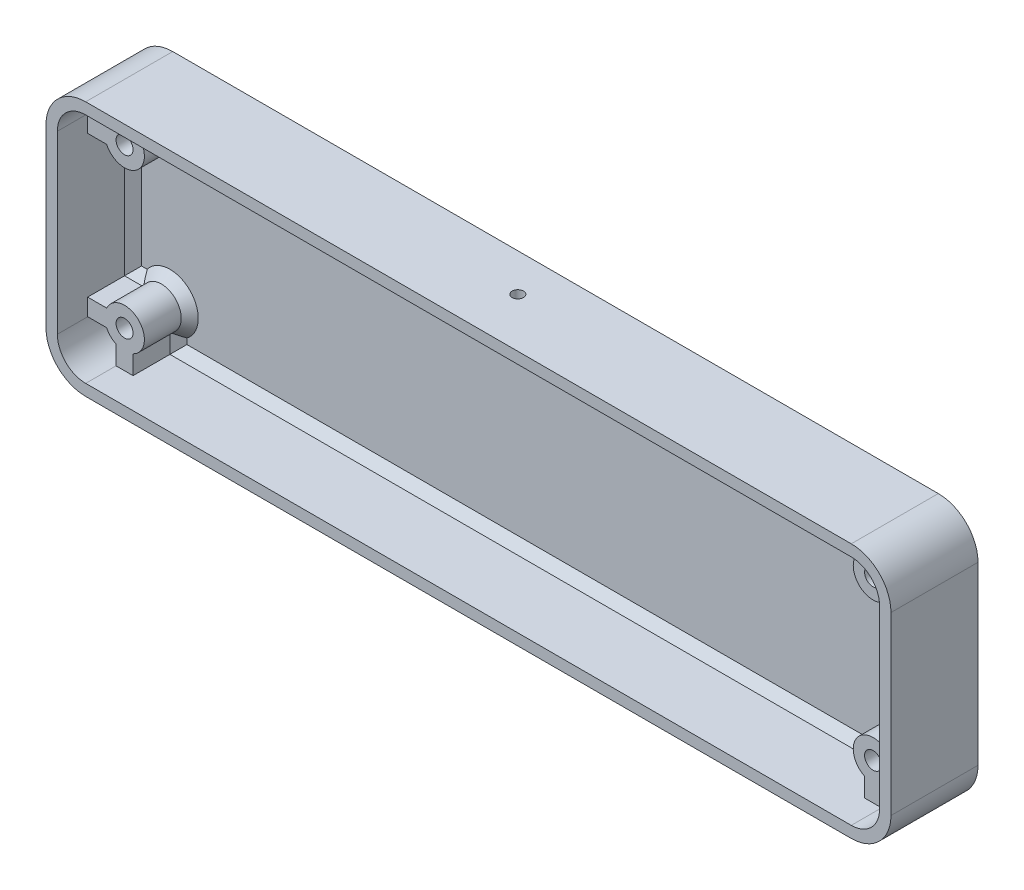
SolidWorks part; units mm, degrees
ref_plane "Alzado" through (0, 0, 0) normal (0, 0, 1) x (1, 0, 0)
ref_plane "Planta" through (0, 0, 0) normal (0, 1, 0) x (1, 0, 0)
ref_plane "Vista lateral" through (0, 0, 0) normal (1, 0, 0) x (0, 0, -1)
sketch "Croquis1" plane through (0, 0, 0) normal (0, 0, 1) x (1, 0, 0)
  line L0 (-67.5, 22.5) -> (67.5, 22.5)
  line L1 (-70, -18) -> (70, -18) construction
  line L2 (-70, -18) -> (-70, 18) construction
  line L3 (-70, 18) -> (70, 18) construction
  line L4 (70, -18) -> (70, 18) construction
  line L5 (-70, -18) -> (70, 18) construction
  line L6 (-70, 18) -> (70, -18) construction
  line L7 (-67.5, 20.5) -> (67.5, 20.5)
  line L8 (-72.5, 15.5) -> (-72.5, -15.5)
  line L9 (-67.5, -20.5) -> (67.5, -20.5)
  line L10 (72.5, 15.5) -> (72.5, -15.5)
  line L11 (-72.5, 20.5) -> (72.5, -20.5) construction
  line L12 (-72.5, -20.5) -> (72.5, 20.5) construction
  line L13 (74.5, 15.5) -> (74.5, -15.5)
  line L14 (-67.5, -22.5) -> (67.5, -22.5)
  line L15 (-74.5, 15.5) -> (-74.5, -15.5)
  arc A0 (67.5, 20.5) -> (72.5, 15.5) centre (67.5, 15.5) cw
  arc A1 (67.5, -20.5) -> (72.5, -15.5) centre (67.5, -15.5) ccw
  arc A2 (-67.5, -20.5) -> (-72.5, -15.5) centre (-67.5, -15.5) cw
  arc A3 (-72.5, 15.5) -> (-67.5, 20.5) centre (-67.5, 15.5) cw
  arc A4 (67.5, 22.5) -> (74.5, 15.5) centre (67.5, 15.5) cw
  arc A5 (67.5, -22.5) -> (74.5, -15.5) centre (67.5, -15.5) ccw
  arc A6 (-67.5, -22.5) -> (-74.5, -15.5) centre (-67.5, -15.5) cw
  arc A7 (-74.5, 15.5) -> (-67.5, 22.5) centre (-67.5, 15.5) cw
  circle A8 centre (66, 14) radius 1.5
  circle A9 centre (66, -14) radius 1.5
  circle A10 centre (-66, 14) radius 1.5
  circle A11 centre (-66, -14) radius 1.5
  circle A12 centre (-66, 14) radius 3.5
  circle A13 centre (66, 14) radius 3.5
  circle A14 centre (66, -14) radius 3.5
  circle A15 centre (-66, -14) radius 3.5
  point P0 (0, 0)
  point P6 (0, 0)
  dimension "D5" = 5
  dimension "D7" = 3
  dimension "D8" = 4
  dimension "D9" = 4
  dimension "D11" = 4
  dimension "D12" = 2
  dimension "D1" = 140
  dimension "D2" = 36
  dimension "D3" = 145
  dimension "D4" = 41
  dimension "D10" = 4
  dimension "D6" = 2
  dimension "D13" = 2
  dimension "D14" = 2
  dimension "D15" = 2
extrude "Saliente-Extruir1" add sketch "Croquis1" against normal blind 15.35 contours A7 L15 A6 L14 A5 L13 A4 L0 L8 A3 L7 A0 L10 A1 L9 A2 | A13 A8 | A14 A9 | A12 A10 | A15 A11 region at (0, 20.9435, 0) region at (-69.401, 14, 0) region at (62.599, 14, 0) region at (62.599, -14, 0) region at (-69.401, -14, 0)
sketch "Croquis3" plane through (0, 0, -15.35) normal (0, 0, -1) x (-1, 0, 0)
  line L0 (72.5, 15.5) -> (72.5, -15.5) construction
  line L1 (67.5, -20.5) -> (-67.5, -20.5) construction
  line L2 (-72.5, 15.5) -> (-72.5, -15.5) construction
  line L3 (67.5, 20.5) -> (-67.5, 20.5) construction
  line L4 (72.5, 15.5) -> (72.5, -15.5)
  line L5 (67.5, -20.5) -> (-67.5, -20.5)
  line L6 (-72.5, 15.5) -> (-72.5, -15.5)
  line L7 (67.5, 20.5) -> (-67.5, 20.5)
  arc A0 (67.5, -20.5) -> (72.5, -15.5) centre (67.5, -15.5) ccw construction
  arc A1 (72.5, 15.5) -> (67.5, 20.5) centre (67.5, 15.5) ccw construction
  arc A2 (-72.5, -15.5) -> (-67.5, -20.5) centre (-67.5, -15.5) ccw construction
  arc A3 (-67.5, 20.5) -> (-72.5, 15.5) centre (-67.5, 15.5) ccw construction
  arc A4 (67.5, -20.5) -> (72.5, -15.5) centre (67.5, -15.5) ccw
  arc A5 (72.5, 15.5) -> (67.5, 20.5) centre (67.5, 15.5) ccw
  arc A6 (-72.5, -15.5) -> (-67.5, -20.5) centre (-67.5, -15.5) ccw
  arc A7 (-67.5, 20.5) -> (-72.5, 15.5) centre (-67.5, 15.5) ccw
extrude "Saliente-Extruir2" add sketch "Croquis3" against normal blind 2
sketch "Croquis5" plane through (0, 0, 0) normal (0, 0, 1) x (1, 0, 0)
  circle A0 centre (66, -14) radius 1.5 construction
  circle A1 centre (66, -14) radius 3.5 construction
  circle A2 centre (66, 14) radius 1.5 construction
  circle A3 centre (66, 14) radius 3.5 construction
  circle A4 centre (-66, -14) radius 1.5 construction
  circle A5 centre (-66, -14) radius 3.5 construction
  circle A6 centre (-66, 14) radius 1.5 construction
  circle A7 centre (-66, 14) radius 3.5 construction
  circle A8 centre (66, -14) radius 1.5
  circle A9 centre (66, -14) radius 3.5
  circle A10 centre (66, 14) radius 1.5
  circle A11 centre (66, 14) radius 3.5
  circle A12 centre (-66, -14) radius 1.5
  circle A13 centre (-66, -14) radius 3.5
  circle A14 centre (-66, 14) radius 1.5
  circle A15 centre (-66, 14) radius 3.5
extrude "Cortar-Extruir1" cut sketch "Croquis5" against normal blind 5.35
sketch "Croquis6" plane through (0, 0, -5.35) normal (0, 0, 1) x (1, 0, 0)
  line L0 (-69.1623, -12.5) -> (-72.5, -12.5)
  line L1 (-72.5, 15.5) -> (-72.5, -15.5) construction
  line L2 (-69.1623, -15.5) -> (-72.5, -15.5)
  line L3 (-72.5, -12.5) -> (-72.5, -15.5)
  line L4 (-68.336, -12.5) -> (-72.5, -12.5) construction
  line L5 (-68.336, -15.5) -> (-72.5, -15.5) construction
  line L6 (-64.5, -17.1623) -> (-64.5, -20.5)
  line L7 (67.5, -20.5) -> (-67.5, -20.5) construction
  line L8 (-67.5, -17.1623) -> (-67.5, -20.5)
  line L9 (-67.5, -16.2401) -> (-67.5, -20.5) construction
  line L10 (-64.5, -16.2401) -> (-64.5, -20.5) construction
  line L11 (-64.5, -20.5) -> (-67.5, -20.5)
  line L12 (-72.5, 12.5) -> (-69.1623, 12.5)
  line L13 (-72.5, -15.5) -> (-72.5, 15.5) construction
  line L14 (-72.5, 15.5) -> (-69.1623, 15.5)
  line L15 (-72.5, 15.5) -> (-72.5, 12.5)
  line L16 (-64.5, 17.1623) -> (-64.5, 20.5)
  line L17 (-67.5, 20.5) -> (67.5, 20.5) construction
  line L18 (-67.5, 17.1623) -> (-67.5, 20.5)
  line L19 (-72.5, 15.5) -> (-66.5585, 15.5) construction
  line L20 (-67.5, 14) -> (-67.5, 20.5) construction
  line L21 (-72.5, 12.5) -> (-66.5585, 12.5) construction
  line L22 (-64.5, 14) -> (-64.5, 20.5) construction
  line L23 (-67.5, 20.5) -> (-64.5, 20.5)
  line L24 (0, 8.9423) -> (0, -8.2588) construction
  line L25 (72.5, -12.5) -> (72.5, -15.5)
  line L26 (69.1623, -12.5) -> (72.5, -12.5)
  line L27 (69.1623, -15.5) -> (72.5, -15.5)
  line L28 (67.5, -17.1623) -> (67.5, -20.5)
  line L29 (64.5, -20.5) -> (67.5, -20.5)
  line L30 (64.5, -17.1623) -> (64.5, -20.5)
  line L31 (72.5, 12.5) -> (69.1623, 12.5)
  line L32 (72.5, 15.5) -> (72.5, 12.5)
  line L33 (72.5, 15.5) -> (69.1623, 15.5)
  line L34 (67.5, 17.1623) -> (67.5, 20.5)
  line L35 (67.5, 20.5) -> (64.5, 20.5)
  line L36 (64.5, 17.1623) -> (64.5, 20.5)
  circle A0 centre (-66, -14) radius 3.5 construction
  arc A1 (-69.1623, -12.5) -> (-69.1623, -15.5) centre (-66, -14) ccw
  circle A2 centre (-66, -14) radius 1.5 construction
  arc A3 (-69.1623, -12.5) -> (-69.1623, -15.5) centre (-66, -14) ccw
  arc A4 (-67.5, -17.1623) -> (-64.5, -17.1623) centre (-66, -14) ccw
  circle A5 centre (66, -14) radius 3.5 construction
  circle A6 centre (66, 14) radius 3.5 construction
  circle A7 centre (-66, 14) radius 3.5 construction
  arc A8 (64.5, -17.1623) -> (67.5, -17.1623) centre (66, -14) ccw
  arc A9 (67.5, 17.1623) -> (64.5, 17.1623) centre (66, 14) ccw
  arc A10 (-64.5, 17.1623) -> (-67.5, 17.1623) centre (-66, 14) ccw
  circle A11 centre (-66, 14) radius 1.5 construction
  circle A12 centre (-66, 14) radius 1.5 construction
  arc A13 (-69.1623, 15.5) -> (-69.1623, 12.5) centre (-66, 14) ccw
  arc A14 (69.1623, -12.5) -> (69.1623, -15.5) centre (66, -14) cw
  arc A15 (67.5, -17.1623) -> (64.5, -17.1623) centre (66, -14) cw
  arc A16 (69.1623, 15.5) -> (69.1623, 12.5) centre (66, 14) cw
  arc A17 (64.5, 17.1623) -> (67.5, 17.1623) centre (66, 14) cw
  arc A18 (69.1623, 12.5) -> (69.1623, 15.5) centre (66, 14) ccw
  arc A19 (69.1623, -15.5) -> (69.1623, -12.5) centre (66, -14) ccw
  circle M4 centre (-66, -14) radius 3.5
  dimension "D1" = 3
  dimension "D2" = 3
  dimension "D3" = 3
  dimension "D4" = 3
extrude "Saliente-Extruir3" add sketch "Croquis6" against normal blind 8 contours L0 L3 L2 M4 | L11 L6 L8 M4 | A13 L14 L15 L12 | A10 L16 L23 L18 | A9 L34 L35 L36 | L33 A16 L31 L32 | L26 A14 L27 L25 | A8 L30 L29 L28 region at (-70.9432, -14, -5.35) region at (-66, -18.9432, -5.35) region at (-70.9432, 14, -5.35) region at (-66, 18.9432, -5.35) region at (70.9432, -14, -5.35) region at (66, -18.9432, -5.35) region at (70.9432, 14, -5.35) region at (66, 18.9432, -5.35)
chamfer "Chaflán1" distance 1.5 angle 45 31 edges at (-70.8311, -12.5, -13.35) (-64.5, -18.8311, -13.35) (-63.5251, -11.5251, -13.35) (-67.5, -18.8311, -13.35) (-68.4749, -16.4749, -13.35) (-70.8311, -15.5, -13.35) (70.8311, -15.5, -13.35) (68.4749, -16.4749, -13.35) (67.5, -18.8311, -13.35) (64.5, -18.8311, -13.35) (63.5251, -11.5251, -13.35) (70.8311, -12.5, -13.35) (70.8311, 15.5, -13.35) (68.4749, 16.4749, -13.35) (67.5, 18.8311, -13.35) (70.8311, 12.5, -13.35) (63.5251, 11.5251, -13.35) (64.5, 18.8311, -13.35) (-70.8311, 15.5, -13.35) (-67.5, 18.8311, -13.35) (-64.5, 18.8311, -13.35) (-63.5251, 11.5251, -13.35) (-70.8311, 12.5, -13.35) (71.0355, -19.0355, -13.35) (71.0355, 19.0355, -13.35) (-71.0355, 19.0355, -13.35) (0, -20.5, -13.35) (72.5, 0, -13.35) (0, 20.5, -13.35) (-72.5, 0, -13.35) (-71.0355, -19.0355, -13.35)
sketch "Croquis7" plane through (0, 22.5, 0) normal (0, 1, 0) x (1, 0, 0)
  line L0 (-67.5, 0) -> (67.5, 0) construction
  circle A0 centre (0, 8.7) radius 1
  point P2 (0, 0)
  dimension "D1" = 2
  dimension "D2" = 8.7
extrude "Cortar-Extruir2" cut sketch "Croquis7" against normal blind 8
